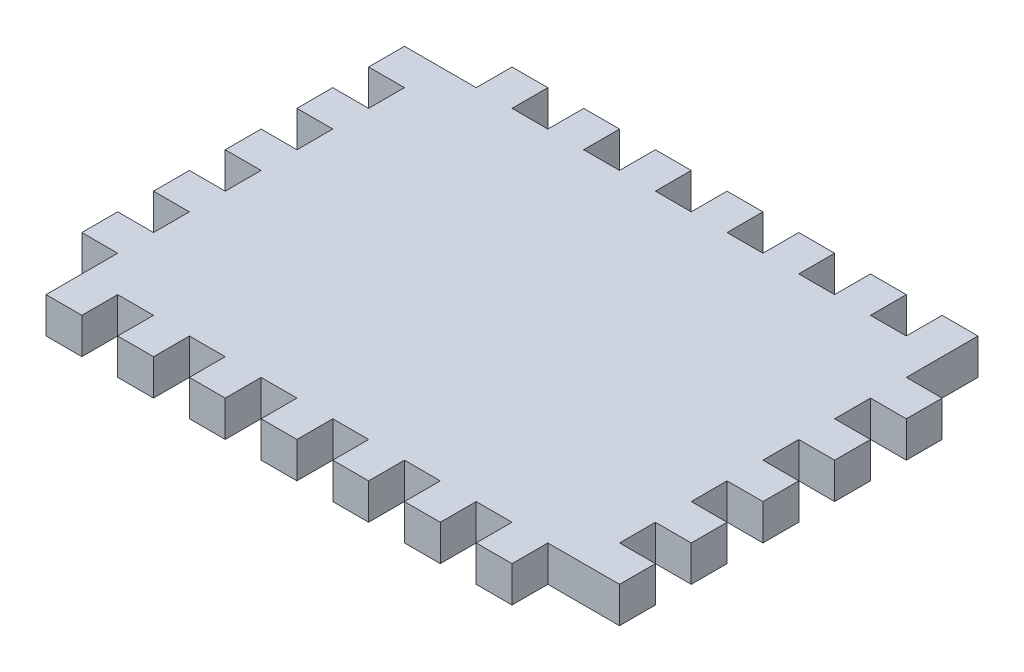
SolidWorks part; units mm, degrees
material "Mahogany"
ref_plane "Front Plane" through (0, 0, 0) normal (0, 0, 1) x (1, 0, 0)
ref_plane "Top Plane" through (0, 0, 0) normal (0, 1, 0) x (1, 0, 0)
ref_plane "Right Plane" through (0, 0, 0) normal (1, 0, 0) x (0, 0, -1)
sketch "Sketch1" plane through (0, 0, 0) normal (0, 1, 0) x (1, 0, 0)
  line L1 (-101.6, 76.2) -> (101.6, 76.2)
  line L2 (-101.6, 76.2) -> (-101.6, -76.2)
  line L3 (-101.6, -76.2) -> (101.6, -76.2)
  line L4 (101.6, 76.2) -> (101.6, -76.2)
  line L5 (-101.6, 76.2) -> (101.6, -76.2) construction
  line L6 (-101.6, -76.2) -> (101.6, 76.2) construction
  point P0 (0, 0)
  dimension "D1" = 203.2
  dimension "D2" = 152.4
extrude "Boss-Extrude1" add sketch "Sketch1" along normal blind 12.7
sketch "Sketch2" plane through (0, 12.7, 0) normal (0, 1, 0) x (1, 0, 0)
  line L0 (101.6, 76.2) -> (-101.6, 76.2) construction
  line L1 (-101.6, 76.2) -> (-76.2, 76.2)
  line L2 (-101.6, 76.2) -> (-101.6, 63.5)
  line L3 (-101.6, 63.5) -> (-76.2, 63.5)
  line L4 (-76.2, 76.2) -> (-76.2, 63.5)
  line L5 (-63.5, 69.85) -> (-76.2, 69.85) construction
  line L6 (-63.5, 76.2) -> (-50.8, 76.2)
  line L7 (-63.5, 76.2) -> (-63.5, 63.5)
  line L8 (-63.5, 63.5) -> (-50.8, 63.5)
  line L9 (-50.8, 76.2) -> (-50.8, 63.5)
  line L10 (-38.1, 76.2) -> (-25.4, 76.2)
  line L11 (-38.1, 76.2) -> (-38.1, 63.5)
  line L12 (-38.1, 63.5) -> (-25.4, 63.5)
  line L13 (-25.4, 76.2) -> (-25.4, 63.5)
  line L14 (101.6, -76.2) -> (101.6, 76.2) construction
  line L15 (-50.8, 69.85) -> (-38.1, 69.85) construction
  line L16 (-25.4, 69.85) -> (-12.7, 69.85) construction
  line L17 (-12.7, 76.2) -> (0, 76.2)
  line L18 (-12.7, 76.2) -> (-12.7, 63.5)
  line L19 (-12.7, 63.5) -> (0, 63.5)
  line L20 (0, 76.2) -> (0, 63.5)
  line L21 (12.7, 76.2) -> (25.4, 76.2)
  line L22 (12.7, 76.2) -> (12.7, 63.5)
  line L23 (12.7, 63.5) -> (25.4, 63.5)
  line L24 (25.4, 76.2) -> (25.4, 63.5)
  line L25 (38.1, 76.2) -> (50.8, 76.2)
  line L26 (38.1, 76.2) -> (38.1, 63.5)
  line L27 (38.1, 63.5) -> (50.8, 63.5)
  line L28 (50.8, 76.2) -> (50.8, 63.5)
  line L29 (63.5, 76.2) -> (76.2, 76.2)
  line L30 (63.5, 76.2) -> (63.5, 63.5)
  line L31 (63.5, 63.5) -> (76.2, 63.5)
  line L32 (76.2, 76.2) -> (76.2, 63.5)
  line L33 (0, 69.85) -> (12.7, 69.85) construction
  line L34 (25.4, 69.85) -> (38.1, 69.85) construction
  line L35 (50.8, 69.85) -> (63.5, 69.85) construction
  line L36 (-101.6, 76.2) -> (-101.6, -76.2) construction
  line L37 (101.6, 76.2) -> (88.9, 76.2)
  line L38 (101.6, 76.2) -> (101.6, 50.8)
  line L39 (101.6, 50.8) -> (88.9, 50.8)
  line L40 (88.9, 76.2) -> (88.9, 50.8)
  line L41 (101.6, 38.1) -> (88.9, 38.1)
  line L42 (101.6, 38.1) -> (101.6, 25.4)
  line L43 (101.6, 25.4) -> (88.9, 25.4)
  line L44 (88.9, 38.1) -> (88.9, 25.4)
  line L45 (95.25, 50.8) -> (95.25, 38.1) construction
  line L46 (101.6, 12.7) -> (88.9, 12.7)
  line L47 (101.6, 12.7) -> (101.6, 0)
  line L48 (101.6, 0) -> (88.9, 0)
  line L49 (88.9, 12.7) -> (88.9, 0)
  line L50 (101.6, -12.7) -> (88.9, -12.7)
  line L51 (101.6, -12.7) -> (101.6, -25.4)
  line L52 (101.6, -25.4) -> (88.9, -25.4)
  line L53 (88.9, -12.7) -> (88.9, -25.4)
  line L54 (101.6, -38.1) -> (88.9, -38.1)
  line L55 (101.6, -38.1) -> (101.6, -50.8)
  line L56 (101.6, -50.8) -> (88.9, -50.8)
  line L57 (88.9, -38.1) -> (88.9, -50.8)
  line L58 (101.6, -63.5) -> (88.9, -63.5)
  line L59 (101.6, -63.5) -> (101.6, -76.2)
  line L60 (101.6, -76.2) -> (88.9, -76.2)
  line L61 (88.9, -63.5) -> (88.9, -76.2)
  line L62 (95.25, 25.4) -> (95.25, 12.7) construction
  line L63 (95.25, 0) -> (95.25, -12.7) construction
  line L64 (95.25, -25.4) -> (95.25, -38.1) construction
  line L65 (95.25, -50.8) -> (95.25, -63.5) construction
  dimension "D1" = 12.7
  dimension "D2" = 12.7
  dimension "D3" = 12.7
  dimension "D4" = 25.4
  dimension "D5" = 12.7
extrude "Cut-Extrude1" cut sketch "Sketch2" against normal through all
ref_axis "Axis1" through (0, 0, 0) along (0, 1, 0)
pattern_circular "CirPattern1" count 2 over 360 about axis through (0, 0, 0) along (0, 1, 0) of "Cut-Extrude1"
